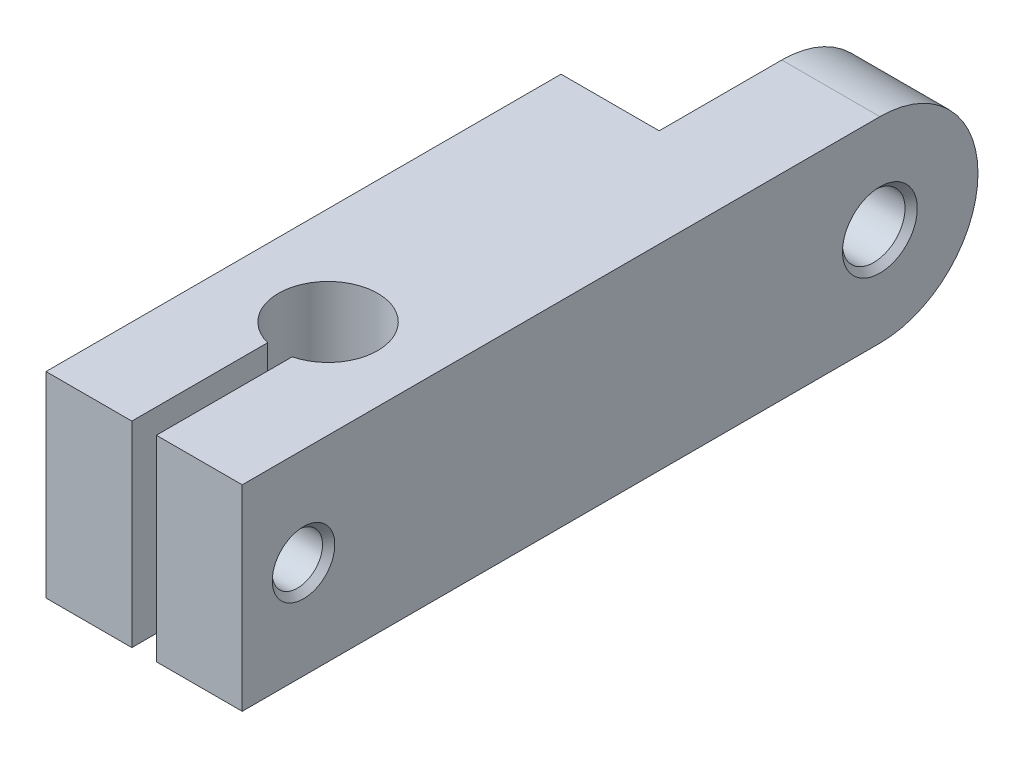
SolidWorks part; units mm, degrees
ref_plane "Front Plane" through (0, 0, 0) normal (0, 0, 1) x (1, 0, 0)
ref_plane "Top Plane" through (0, 0, 0) normal (0, 1, 0) x (1, 0, 0)
ref_plane "Right Plane" through (0, 0, 0) normal (1, 0, 0) x (0, 0, -1)
sketch "Sketch1" plane through (0, 0, 0) normal (0, 0, 1) x (1, 0, 0)
  line L1 (8, -8) -> (-8, -8)
  line L2 (8, -8) -> (8, 8)
  line L3 (8, 8) -> (-8, 8)
  line L4 (-8, -8) -> (-8, 8)
  line L5 (8, -8) -> (-8, 8) construction
  line L6 (8, 8) -> (-8, -8) construction
  point P0 (0, 0)
extrude "Base" add sketch "Sketch1" along normal blind 60
sketch "Sketch2" plane through (0, 8, 0) normal (0, 1, 0) x (1, 0, 0)
  line L0 (-1, -60) -> (-1, -48.9246)
  line L1 (8, -60) -> (-8, -60) construction
  line L2 (1, -60) -> (1, -48.9246)
  line L3 (0, 0) -> (0, -9.2456) construction
  circle A0 centre (0, -45) radius 4.05
  line M6 (-8, -60) -> (8, -60)
  dimension "D1" = 8.1
  dimension "D2" = 15
  dimension "D3" = 2
extrude "IndicatorHole" cut sketch "Sketch2" against normal through all contours A0 | A0 L0 L2 M6 region at (0, 8, 54.5042) region at (0, 8, 45)
sketch "Sketch3" plane through (8, 0, 0) normal (1, 0, 0) x (0, 0, -1)
  line L0 (-60, -8) -> (-60, 8) construction
  circle A0 centre (-55, 0) radius 2.05
  dimension "D1" = 4.1
  dimension "D2" = 5
extrude "IndicatorMount" cut sketch "Sketch3" against normal up to next
chamfer "ChamferIndicatorMount" distance 0.5 angle 45 1 edges at (8, 0, 52.95)
hole_wizard "M4x0.7 Tapped Hole for IndicatorScrew" positions "Sketch4" profile "Sketch5" tap size "M4x0.7" standard "ANSI Metric"
sketch "Sketch4" plane through (-8, 0, 0) normal (-1, 0, 0) x (0, 0, 1)
  point P0 (55, 0)
cosmetic thread "Hole Thread1" parameters "D1"=7, "D2"=4
sketch "Sketch5" plane through (-8, 0, 55) normal (0, 1, 0) x (0, 0, 1)
  line L0 (0, 0) -> (0, 8.9)
  line L1 (0, 8.9) -> (1.65, 7.9086)
  line L2 (1.65, 7.9086) -> (1.65, 0)
  line L5 (1.65, 0) -> (0, 0)
  line L10 (0, 8.9) -> (-1.65, 7.9086) construction
  line L11 (0, -6.35) -> (0, 107.95) construction
  dimension "Tap Drill Dia." = 3.3
  dimension "Tap Drill Depth" = 8.9
  dimension "Drill Angle" = 118
sketch "Sketch6" plane through (0, 0, 0) normal (1, 0, 0) x (0, 0, -1)
  line L0 (-60, -8) -> (0, -8) construction
  line L1 (-18, 8) -> (1.869, 8)
  line L2 (-18, 8) -> (-18, -8)
  line L3 (-18, -8) -> (1.869, -8)
  line L4 (1.869, 8) -> (1.869, -8)
  line L5 (-60, 8) -> (0, 8) construction
  line L6 (0, -8) -> (0, 8) construction
  circle A0 centre (-8, 0) radius 8
  dimension "D2" = 16
  dimension "D1" = 18
extrude "SlotForAnotherPart" cut sketch "Sketch6" against normal through all contours A0 L1 L2 L3 | A0 | A0 L3 L4 L1 region at (0, 7.8113, 13) region at (0, 7.812, 3.0655) region at (0, 0, 8)
extrude "ChamferForSlot" cut sketch "Sketch6<3>" along normal through all contours A0 L3 L4 L1 region at (0, 7.812, 3.0655)
sketch "Sketch6<3>" plane through (0, 0, 0) normal (1, 0, 0) x (0, 0, -1) same geometry as "Sketch6"
sketch "Sketch7" plane through (8, 0, 0) normal (1, 0, 0) x (0, 0, -1)
  circle A0 centre (-8, 0) radius 2.55
  dimension "D1" = 5.1
extrude "ScrewHoleForSlot" cut sketch "Sketch7" against normal through all
chamfer "ChamferForScrewSlot" distance 0.5 angle 45 1 edges at (8, 0, 5.45)
equation "\"D2@Sketch1\"=\"D1@Sketch1\""
